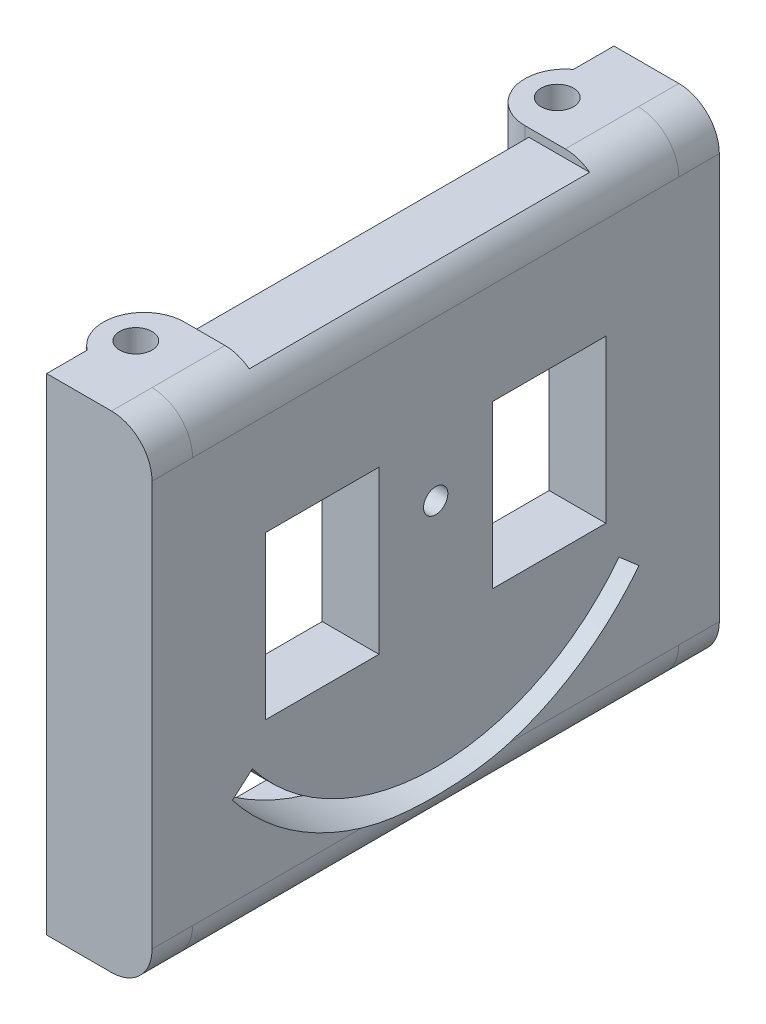
SolidWorks part; units mm, degrees
ref_plane "前视基准面" through (0, 0, 0) normal (0, 0, 1) x (1, 0, 0)
ref_plane "上视基准面" through (0, 0, 0) normal (0, 1, 0) x (1, 0, 0)
ref_plane "右视基准面" through (0, 0, 0) normal (1, 0, 0) x (0, 0, -1)
sketch "草图1" plane through (0, 0, 0) normal (0, 0, 1) x (1, 0, 0)
  line L1 (0, 0) -> (15, 0)
  line L2 (0, 0) -> (0, 60)
  line L3 (0, 60) -> (15, 60)
  line L4 (15, 0) -> (15, 60)
  line L5 (0, 55) -> (8, 55)
  line L6 (0, 55) -> (0, 5)
  line L7 (0, 5) -> (8, 5)
  line L8 (8, 55) -> (8, 5)
  dimension "D1" = 60
  dimension "D2" = 15
  dimension "D3" = 5
  dimension "D4" = 7
  dimension "D5" = 5
extrude "凸台-拉伸1" add sketch "草图1" along normal blind 62 contours L5 L8 L7 L2 L1 L4 L3 region at (10.3, 30, 0)
fillet "圆角1" radius 5 2 edges at (15, 0, 31) (15, 60, 31)
sketch "草图2" plane through (15, 0, 0) normal (1, 0, 0) x (0, 0, -1)
  line L0 (-62, 60) -> (0, 60) construction
  line L1 (-52, 60) -> (-10, 60)
  line L2 (-52, 60) -> (-52, 59)
  line L3 (-52, 59) -> (-10, 59)
  line L4 (-10, 60) -> (-10, 59)
  line L5 (-62, 60) -> (-62, 55) construction
  line L6 (0, 55) -> (0, 60) construction
  dimension "D1" = 1
  dimension "D2" = 10
  dimension "D3" = 10
extrude "切除-拉伸1" cut sketch "草图2" against normal blind 62
sketch "草图3" plane through (0, 60, 0) normal (0, 1, 0) x (1, 0, 0)
  line L0 (10, -62) -> (10, -52) construction
  line L1 (0, -52) -> (10, -52) construction
  line L2 (0, -10) -> (10, -10) construction
  circle A0 centre (4, -57) radius 2
  circle A1 centre (4, -5) radius 2
  dimension "D1" = 6
  dimension "D2" = 5
  dimension "D4" = 4
  dimension "D5" = 4
  dimension "D3" = 5
extrude "切除-拉伸2" cut sketch "草图3" against normal blind 62
sketch "草图4" plane through (0, 0, 0) normal (-1, 0, 0) x (0, 0, 1)
  line L1 (10, 57.021) -> (52, 57.021)
  line L2 (10, 57.021) -> (10, 55)
  line L3 (10, 55) -> (52, 55)
  line L4 (52, 57.021) -> (52, 55)
  line L7 (62, 55) -> (0, 55) construction
  dimension "D1" = 2.021
extrude "切除-拉伸3" cut sketch "草图4" against normal up to surface (8 mm away) up to face at (8, 30, 31)
sketch "草图5" plane through (0, 60, 0) normal (0, 1, 0) x (1, 0, 0)
  line L0 (0, -62) -> (0, -52) construction
  line L1 (0, -52) -> (10, -52) construction
  line L2 (0, -10) -> (0, 0) construction
  line L3 (0, -10) -> (10, -10) construction
  line L4 (5, 0) -> (0, 0)
  line L5 (0, 0) -> (0, -5)
  line L6 (0, -5) -> (0, -10)
  line L7 (0, -10) -> (5, -10)
  line L8 (5, -52) -> (0, -52)
  line L9 (0, -52) -> (0, -57)
  line L10 (0, -57) -> (0, -62)
  line L11 (0, -62) -> (5, -62)
  circle A0 centre (5, -57) radius 5
  circle A1 centre (5, -5) radius 5
  line M4 (10, -52) -> (0, -52)
  line M5 (0, -52) -> (0, -62)
  line M6 (0, -62) -> (10, -62)
  dimension "D1" = 10
  dimension "D2" = 10
extrude "切除-拉伸4" cut sketch "草图5" against normal blind 62 contours A1 L4 L5 | A1 L6 L7 | A0 M4 M5 | A0 M5 M6 region at (1.1168, 60, 1.1168) region at (1.1168, 60, 8.8832) region at (1.1168, 60, 53.1168) region at (1.1168, 60, 60.8832)
sketch "草图6" plane through (0, 59, 0) normal (0, 1, 0) x (1, 0, 0)
  line L0 (4, -10) -> (4, -52)
  line L3 (4, -52) -> (13, -52)
  line L4 (13, -52) -> (13, -10)
  line L5 (13, -10) -> (4, -10)
  line L6 (0, -10) -> (4, -10)
  line L7 (4, -52) -> (0, -52)
  line L8 (0, -52) -> (0, -10)
  line M5 (0, -10) -> (0, -52)
  line M6 (0, -52) -> (5, -52)
  line M10 (5, -10) -> (0, -10)
  dimension "D1" = 9
extrude "切除-拉伸5" cut sketch "草图6" against normal blind 62 contours L0 M10 M5 M6 region at (2, 59, 31)
sketch "草图8" plane through (8, 0, 0) normal (-1, 0, 0) x (0, 0, 1)
  line L0 (31, 61.2864) -> (31, -8.1965) construction
  line L1 (10, 59) -> (52, 59) construction
  line L2 (10, 42.5) -> (24, 42.5)
  line L3 (10, 42.5) -> (10, 22.5)
  line L4 (10, 22.5) -> (24, 22.5)
  line L5 (24, 42.5) -> (24, 22.5)
  line L6 (0, 55) -> (0, 5) construction
  line L7 (52, 22.5) -> (38, 22.5)
  line L8 (38, 42.5) -> (38, 22.5)
  line L9 (52, 42.5) -> (38, 42.5)
  line L10 (52, 42.5) -> (52, 22.5)
  line L11 (10, 0.4174) -> (52, 0.4174) construction
  line L14 (8.3818, 18.0776) -> (5.9187, 15.9427)
  line L15 (53.6182, 18.0776) -> (56.0813, 15.9427)
  circle A0 centre (31, 35.4174) radius 1.5
  arc A3 (8.3818, 18.0776) -> (53.6182, 18.0776) centre (31, 35.4174) ccw
  arc A4 (5.9187, 15.9427) -> (56.0813, 15.9427) centre (31, 35.4174) ccw
  point P17 (31, 6.9174)
  dimension "D5" = 3
  dimension "D1" = 16.5
  dimension "D2" = 20
  dimension "D3" = 10
  dimension "D4" = 14
  dimension "D6" = 28.5
  dimension "D7" = 35
extrude "切除-拉伸7" cut sketch "草图8" against normal through all
sketch "草图9" plane through (0, 59, 0) normal (0, 1, 0) x (1, 0, 0)
  line L0 (5, -52) -> (13, -52) construction
  line L1 (4, -10) -> (5.5, -10)
  line L2 (4, -10) -> (4, -52)
  line L3 (4, -52) -> (5.5, -52)
  line L4 (5.5, -10) -> (5.5, -52)
  dimension "D1" = 1.5
extrude "切除-拉伸8" cut sketch "草图9" against normal up to next
sketch "草图11" plane through (0, 60, 0) normal (0, 1, 0) x (1, 0, 0)
  line L0 (-37.6455, -31) -> (31.1561, -31) construction
  line L1 (15, -62) -> (1.4935, -62)
  line L2 (15, -62) -> (15, -61)
  line L3 (15, -61) -> (1.4935, -61)
  line L4 (1.4935, -62) -> (1.4935, -61)
  line L5 (15, -1) -> (1.4935, -1)
  line L6 (1.4935, 0) -> (1.4935, -1)
  line L7 (15, 0) -> (1.4935, 0)
  line L8 (15, 0) -> (15, -1)
  point P5 (8.2468, -61)
  point P9 (-3.2447, -31)
  dimension "D1" = 1
extrude "切除-拉伸10" cut sketch "草图11" against normal through all
sketch "草图12" plane through (15, 0, 0) normal (1, 0, 0) x (0, 0, -1)
  line L1 (-1, 55) -> (4, 55)
  line L2 (-1, 55) -> (-1, 5)
  line L3 (-1, 5) -> (4, 5)
  line L4 (4, 55) -> (4, 5)
  dimension "D1" = 5
  dimension "D2" = 50
sketch "草图13" plane through (0, 0, 1) normal (0, 0, -1) x (-1, 0, 0)
  line L1 (-2, 60) -> (-15, 60)
  line L2 (-2, 60) -> (-2, 0)
  line L3 (-2, 0) -> (-15, 0)
  line L4 (-15, 60) -> (-15, 0)
  dimension "D1" = 13
  dimension "D2" = 60
extrude "凸台-拉伸5" add sketch "草图13" along normal blind 5
fillet "圆角2" radius 5 2 edges at (15, 0, -1.5) (15, 60, -1.5)
sketch "草图14" plane through (0, 0, 61) normal (0, 0, 1) x (1, 0, 0)
  line L1 (2, 60) -> (15, 60)
  line L2 (2, 60) -> (2, 0)
  line L3 (2, 0) -> (15, 0)
  line L4 (15, 60) -> (15, 0)
  dimension "D1" = 60
  dimension "D2" = 13
extrude "凸台-拉伸6" add sketch "草图14" along normal blind 5
fillet "圆角3" radius 5 2 edges at (15, 0, 63.5) (15, 60, 63.5)
sketch "草图15" plane through (2, 0, 0) normal (-1, 0, 0) x (0, 0, 1)
  line L1 (1, 5) -> (0.6, 5)
  line L2 (1, 5) -> (1, 55)
  line L3 (1, 55) -> (0.6, 55)
  line L4 (0.6, 5) -> (0.6, 55)
  dimension "D1" = 50
  dimension "D2" = 0.4
extrude "切除-拉伸11" cut sketch "草图15" against normal blind 6 contours L2 L1 L4 L3
sketch "草图17" plane through (2, 0, 0) normal (-1, 0, 0) x (0, 0, 1)
  line L1 (61, 5) -> (61.4, 5)
  line L2 (61, 5) -> (61, 55)
  line L3 (61, 55) -> (61.4, 55)
  line L4 (61.4, 5) -> (61.4, 55)
  dimension "D1" = 50
  dimension "D2" = 0.4
